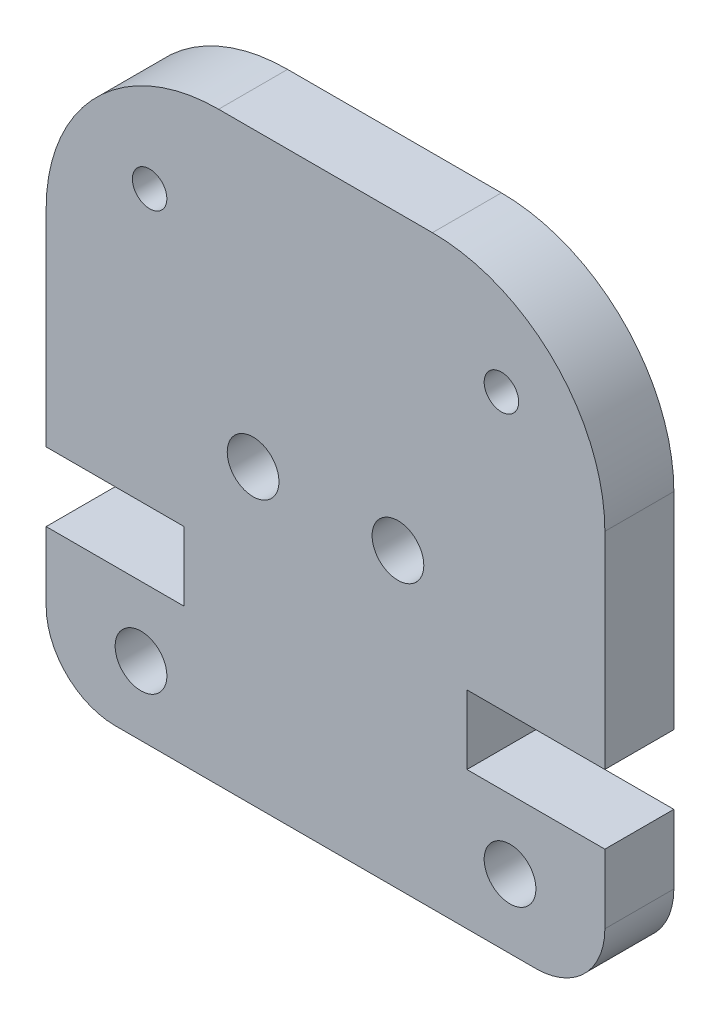
SolidWorks part; units mm, degrees
ref_plane "Front Plane" through (0, 0, 0) normal (0, 0, 1) x (1, 0, 0)
ref_plane "Top Plane" through (0, 0, 0) normal (0, 1, 0) x (1, 0, 0)
ref_plane "Right Plane" through (0, 0, 0) normal (1, 0, 0) x (0, 0, -1)
sketch "Sketch1" plane through (0, 0, 0) normal (0, 0, 1) x (1, 0, 0)
  line L0 (0, 16.98) -> (0, 0) construction
  line L1 (3.1, 16.98) -> (-3.1, 16.98)
  line L2 (6.1, 0) -> (-6.1, 0)
  line L3 (-8.1, 6) -> (-4.1, 6)
  line L4 (-4.1, 6) -> (-4.1, 4)
  line L5 (-4.1, 4) -> (-8.1, 4)
  line L6 (-8.1, 2) -> (-8.1, 4)
  line L7 (8.1, 11.98) -> (8.1, 6)
  line L8 (-8.1, 11.98) -> (-8.1, 6)
  line L24 (8.1, 2) -> (8.1, 4)
  line L27 (4.1, 4) -> (8.1, 4)
  line L30 (4.1, 6) -> (4.1, 4)
  line L31 (8.1, 6) -> (4.1, 6)
  circle A0 centre (-5.35, 2) radius 0.75
  circle A1 centre (-5.1, 13.98) radius 0.5
  arc A2 (-8.1, 11.98) -> (-3.1, 16.98) centre (-3.1, 11.98) cw
  arc A3 (-6.1, 0) -> (-8.1, 2) centre (-6.1, 2) cw
  circle A4 centre (-2.1, 8.5) radius 0.75
  circle A10 centre (2.1, 8.5) radius 0.75
  arc A12 (6.1, 0) -> (8.1, 2) centre (6.1, 2) ccw
  arc A14 (8.1, 11.98) -> (3.1, 16.98) centre (3.1, 11.98) ccw
  circle A16 centre (5.1, 13.98) radius 0.5
  circle A18 centre (5.35, 2) radius 0.75
  dimension "D1" = 1.5
  dimension "D2" = 1
  dimension "D3" = 16.98
  dimension "D4" = 2
  dimension "D5" = 5
  dimension "D6" = 6.1
  dimension "D7" = 3
  dimension "D8" = 3
  dimension "D9" = 6
  dimension "D10" = 8.5
extrude "Boss-Extrude1" add sketch "Sketch1" along normal blind 2
equation "\"D6@Sketch1\"= ( \"fingerWidth@parametersSketch@prostheticParameters.SLDPRT\" - 4 ) / 2 'Finger Width - Radius"
equation "\"D3@Sketch1\"= ( \"HL@parametersSketch@prostheticParameters.SLDPRT\" * 0.108 ) - 3 'DIP Legth-Sil. Sh. DIP"
